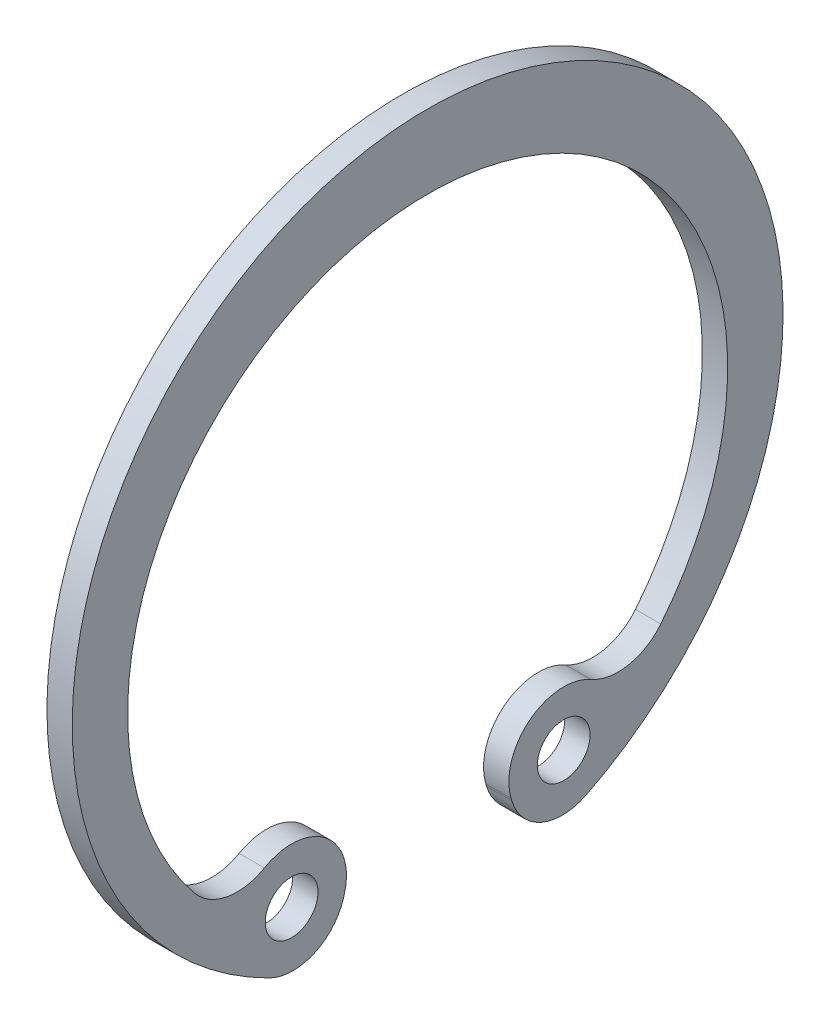
SolidWorks part; units mm, degrees
ref_plane "Front Plane" through (0, 0, 0) normal (0, 0, 1) x (1, 0, 0)
ref_plane "Top Plane" through (0, 0, 0) normal (0, 1, 0) x (1, 0, 0)
ref_plane "Right Plane" through (0, 0, 0) normal (1, 0, 0) x (0, 0, -1)
ref_plane "Plane1" through (0, 0, 0) normal (1, 0, 0) x (0, 0, -1)
sketch "Sketch1" plane through (0, 0, 0) normal (1, 0, 0) x (0, 0, -1)
  line L0 (-3.9896, -13.5557) -> (-3.9558, -13.4408)
  line L1 (3.9558, -13.4408) -> (3.9896, -13.5557)
  arc A0 (7.5008, -15.0884) -> (-7.5008, -15.0884) centre (0, 0) ccw
  arc A1 (-7.5008, -15.0884) -> (-3.9896, -13.5557) centre (-6.3879, -12.8498) ccw
  arc A2 (-3.9558, -13.4408) -> (-7.7412, -10.45) centre (-6.45, -12.7067) ccw
  arc A3 (-7.7412, -10.45) -> (-11.0525, -9.83) centre (-9.0324, -8.1932) cw
  arc A4 (-11.0525, -9.83) -> (11.0525, -9.83) centre (0, -0.875) cw
  arc A5 (11.0525, -9.83) -> (7.7412, -10.45) centre (9.0324, -8.1932) cw
  arc A6 (7.7412, -10.45) -> (3.9558, -13.4408) centre (6.45, -12.7067) ccw
  arc A7 (3.9896, -13.5557) -> (7.5008, -15.0884) centre (6.3879, -12.8498) ccw
  circle A8 centre (6.45, -12.7067) radius 1.25
  circle A9 centre (-6.45, -12.7067) radius 1.25
extrude "Boss-Extrude1" add sketch "Sketch1" against normal blind 0.6 and the other way blind 0.6
